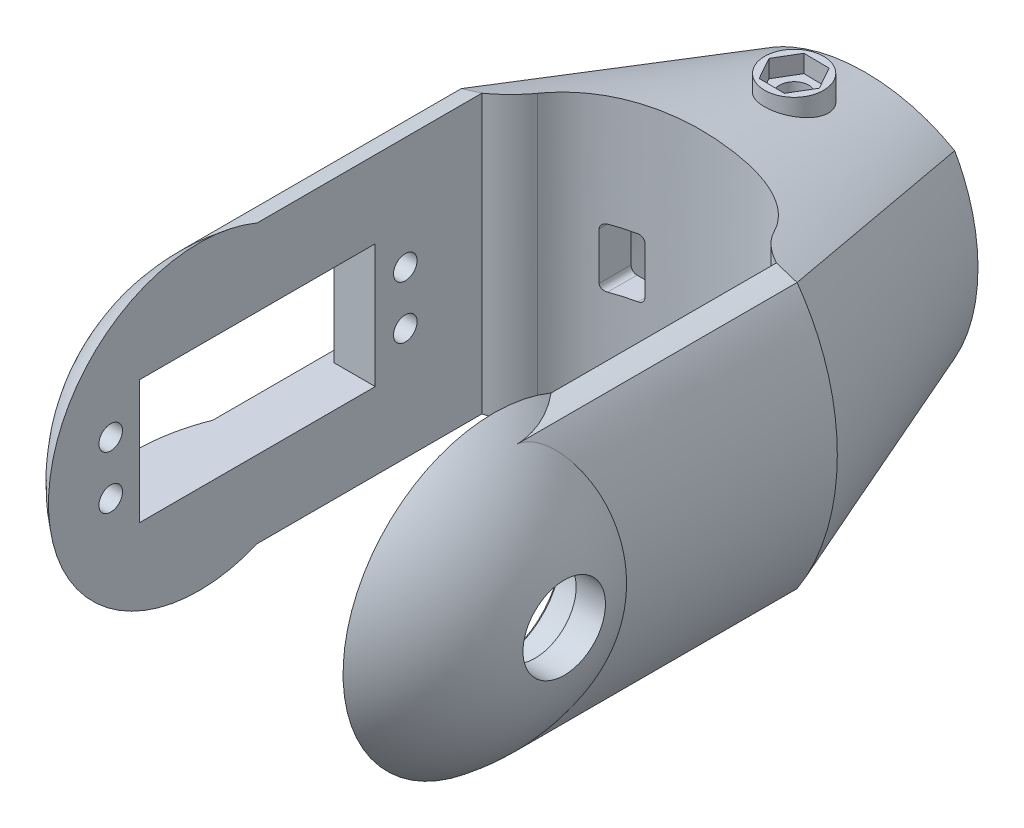
SolidWorks part; units mm, degrees
ref_plane "Front Plane" through (0, 0, 0) normal (0, 0, 1) x (1, 0, 0)
ref_plane "Top Plane" through (0, 0, 0) normal (0, 1, 0) x (1, 0, 0)
ref_plane "Right Plane" through (0, 0, 0) normal (1, 0, 0) x (0, 0, -1)
ref_plane "Plane1" through (0, 0, -10) normal (0, 0, 1) x (1, 0, 0)
sketch "Sketch1" plane through (0, 0, -10) normal (0, 0, 1) x (1, 0, 0)
  line L0 (0, 0) -> (0, -8.0613) construction
  line L1 (0, 0) -> (40.2646, 0) construction
  spline S0 degree 3 poles (15.25, 15.25) (6.016, 20.5606) (-6.0211, 20.458) (-15.25, 15.25) knots 0 0 0 0 1 1 1 1
  spline S1 degree 3 poles (-15.25, 15.25) (-20.5331, 5.9894) (-20.5168, -5.9855) (-15.25, -15.25) knots 0 0 0 0 1 1 1 1
  spline S2 degree 3 poles (15.25, 15.25) (20.5331, 5.9894) (20.5168, -5.9855) (15.25, -15.25) knots 0 0 0 0 1 1 1 1
  spline S3 degree 3 poles (15.25, -15.25) (6.016, -20.5606) (-6.0211, -20.458) (-15.25, -15.25) knots 0 0 0 0 1 1 1 1
ref_plane "Plane2" through (0, 0, 30) normal (0, 0, 1) x (1, 0, 0)
sketch "Sketch2" plane through (0, 0, 30) normal (0, 0, 1) x (1, 0, 0)
  line L0 (0, 0) -> (0, -8.0613) construction
  line L1 (0, 0) -> (40.2646, 0) construction
  spline S0 degree 3 poles (28.5, -22.5) (10.4221, -28.8227) (-10.3532, -28.5006) (-28.5, -22.5) knots 0 0 0 0 1 1 1 1
  spline S1 degree 3 poles (-28.5, -22.5) (-37.1361, -9.2774) (-38.0618, 9.2688) (-28.5, 22.5) knots 0 0 0 0 1 1 1 1
  spline S2 degree 3 poles (28.5, -22.5) (37.1361, -9.2774) (38.0618, 9.2688) (28.5, 22.5) knots 0 0 0 0 1 1 1 1
  spline S3 degree 3 poles (28.5, 22.5) (10.4221, 28.8227) (-10.3532, 28.5006) (-28.5, 22.5) knots 0 0 0 0 1 1 1 1
loft "Loft3" add profiles "Sketch1", "Sketch2" connector at (-15.25, -15.25, -10) connector at (-28.5, -22.5, 30)
extrude "Boss-Extrude3" add sketch "Sketch2<4>" along normal blind 48
sketch "Sketch2<4>" plane through (0, 0, 30) normal (0, 0, 1) x (1, 0, 0) same geometry as "Sketch2"
sketch "Sketch6" plane through (0, 0, 0) normal (0, 1, 0) x (1, 0, 0)
  line L0 (-37.75, -78) -> (37.75, -78)
  line L1 (-5.75, -110) -> (5.75, -110)
  line L2 (0, 0) -> (0, -78) construction
  line L3 (-28.5, -78) -> (28.5, -78) construction
  arc A0 (5.75, -110) -> (37.75, -78) centre (5.75, -78) ccw
  arc A1 (-5.75, -110) -> (-37.75, -78) centre (-5.75, -78) cw
  dimension "D1" = 32
  dimension "D3" = 11.5
sketch "Sketch5" plane through (0, 0, 0) normal (0, 1, 0) x (1, 0, 0)
  line L0 (-21.5, -30) -> (-25, -30)
  line L4 (-25, -121.923) -> (25, -121.923)
  line L5 (0, -107.2446) -> (0, 0) construction
  line L6 (28.5, -30) -> (-28.5, -30) construction
  line L9 (-25, -30) -> (-25, -121.923)
  line L10 (21.5, -30) -> (25, -30)
  line L11 (25, -30) -> (25, -121.923)
  spline S0 degree 3 poles (-21.5, -30) (-20.9607, -25.8176) (-17.1377, -20.1269) (-5.2121, -17.7955) (5.5443, -17.9718) (16.9214, -19.6712) (21.5048, -26.7681) (21.5, -30) knots 0 0 0 0 0.183276 0.396096 0.580775 0.804186 1 1 1 1
  point P26 (0, -121.923)
  dimension "D3" = 33
  dimension "D4" = 16.5
  dimension "D1" = 10
  dimension "D2" = 5
  dimension "D5" = 40
  dimension "D6" = 20
  dimension "D7" = 21.5
  dimension "D8" = 43
  dimension "D9" = 50
revolve "Revolve2" add sketch "Sketch6" angle 360 about L0
extrude "Cut-Extrude2" cut sketch "Sketch5" against normal blind 57 and the other way blind 54 contours L5 L4 S0 | L4 L5 S0 region at (0.0026, 0, 71.6291)
ref_plane "Plane3" through (-40, 0, 0) normal (1, 0, 0) x (0, 0, -1)
sketch "Sketch8" plane through (-40, 0, 0) normal (1, 0, 0) x (0, 0, -1)
  line L1 (-95, -10.5) -> (-41, -10.5)
  line L2 (-95, -10.5) -> (-95, 10.5)
  line L3 (-95, 10.5) -> (-41, 10.5)
  line L4 (-41, -10.5) -> (-41, 10.5)
  dimension "D1" = 41
  dimension "D2" = 21
  dimension "D3" = 10.5
  dimension "D4" = 54
extrude "Cut-Extrude4" cut sketch "Sketch8" along normal blind 8
sketch "Sketch24" plane through (-32, 0, 0) normal (-1, 0, 0) x (0, 0, 1)
  line L1 (48.1, 10.5) -> (88.1, 10.5)
  line L2 (48.1, 10.5) -> (48.1, -10.5)
  line L3 (48.1, -10.5) -> (88.1, -10.5)
  line L4 (88.1, 10.5) -> (88.1, -10.5)
  dimension "D1" = 40
  dimension "D2" = 21
  dimension "D3" = 10.5
  dimension "D4" = 88.1
extrude "Cut-Extrude13" cut sketch "Sketch24" against normal blind 32
sketch "Sketch21" plane through (0, 0, 0) normal (0, 1, 0) x (1, 0, 0)
  circle A0 centre (0, -2) radius 5
  dimension "D2" = 10
  dimension "D1" = 2
extrude "Boss-Extrude4" add sketch "Sketch21" along normal blind 25 and the other way blind 23
sketch "Sketch25" plane through (0, 25, 0) normal (0, 1, 0) x (1, 0, 0)
  line L1 (-2.1207, 1.7753) -> (-4.3298, -1.9489)
  line L2 (-4.3298, -1.9489) -> (-2.2091, -5.7242)
  line L3 (-2.2091, -5.7242) -> (2.1207, -5.7753)
  line L4 (2.1207, -5.7753) -> (4.3298, -2.0511)
  line L5 (4.3298, -2.0511) -> (2.2091, 1.7242)
  line L6 (2.2091, 1.7242) -> (-2.1207, 1.7753)
  circle A0 centre (0, -2) radius 3.75 construction
  circle A1 centre (0, -2) radius 5 construction
  dimension "D1" = 7.5
extrude "Cut-Extrude14" cut sketch "Sketch25" against normal blind 3
sketch "Sketch26" plane through (0, 22, 0) normal (0, 1, 0) x (1, 0, 0)
  circle A0 centre (0, -2) radius 2.5
  circle A1 centre (0, -2) radius 5 construction
  dimension "D1" = 5
extrude "Cut-Extrude15" cut sketch "Sketch26" against normal blind 76
sketch "Sketch20" plane through (0, 0, -10) normal (0, 0, -1) x (-1, 0, 0)
  circle A0 centre (0, 0) radius 15.5
  dimension "D1" = 31
extrude "Cut-Extrude10" cut sketch "Sketch20" against normal blind 25
sketch "Sketch22" plane through (0, 0, 15) normal (0, 0, -1) x (-1, 0, 0)
  line L1 (-8.6714, 5) -> (-14.6714, 5)
  line L2 (-8.6714, 5) -> (-8.6714, -5)
  line L3 (-8.6714, -5) -> (-14.6714, -5)
  line L4 (-14.6714, 5) -> (-14.6714, -5)
  line L5 (8.6714, 5) -> (14.6714, 5)
  line L6 (8.6714, 5) -> (8.6714, -5)
  line L7 (8.6714, -5) -> (14.6714, -5)
  line L8 (14.6714, 5) -> (14.6714, -5)
  circle A2 centre (0, 0) radius 15.5 construction
  circle A3 centre (0, 0) radius 15.5 construction
  point P8 (0, 0)
  point P12 (0, 0)
  dimension "D1" = 10
  dimension "D2" = 6
  dimension "D3" = 6
  dimension "D4" = 5
extrude "Cut-Extrude12" cut sketch "Sketch22" against normal blind 6
ref_plane "Plane4" through (0, 0, 78) normal (0, 0, 1) x (1, 0, 0)
sketch "Sketch23" plane through (0, 0, 78) normal (0, 0, 1) x (1, 0, 0)
  line L0 (21.5, 0) -> (43.8495, 0)
  line L2 (43.8495, 0) -> (43.8495, 7)
  line L3 (43.8495, 7) -> (32, 7)
  line L4 (32, 7) -> (32, 11)
  line L5 (32, 11) -> (25, 11)
  line L7 (25, 11) -> (25, 5)
  line L8 (25, 25.5624) -> (25, -25.5624) construction
  line L9 (21.5, 0) -> (-37.5422, 0)
  line L11 (25, 5) -> (-37.5422, 5)
  line L12 (-37.5422, 0) -> (-37.5422, 5)
  point P2 (25, 8)
  dimension "D1" = 5
  dimension "D2" = 7
  dimension "D3" = 11
  dimension "D4" = 7
revolve "Cut-Revolve1" cut sketch "Sketch23" angle 360 about L0
fillet "Fillet1" radius 10 2 edges
chamfer "Chamfer1" distance 0.5 angle 45 1 edges at (25, -11, 78)
sketch "Sketch27" plane through (-32, 0, 0) normal (-1, 0, 0) x (0, 0, 1)
  circle A0 centre (43, 4.5) radius 2
  circle A1 centre (43, -4.5) radius 2
  circle A2 centre (93, 4.5) radius 2
  circle A3 centre (93, -4.5) radius 2
  dimension "D1" = 4
  dimension "D2" = 4
  dimension "D3" = 4
  dimension "D4" = 4
  dimension "D5" = 9
  dimension "D6" = 4.5
  dimension "D7" = 93
  dimension "D8" = 50
extrude "Cut-Extrude16" cut sketch "Sketch27" against normal blind 10
fillet "Fillet2" radius 1 8 edges at (-8.6714, 5, 16.8268) (-8.6714, -5, 16.8268) (8.6714, 5, 16.7925) (8.6714, -5, 16.7925) (-14.6714, -5, 17.7131) (-14.6714, 5, 17.7131) (14.6714, 5, 17.674) (14.6714, -5, 17.674)
